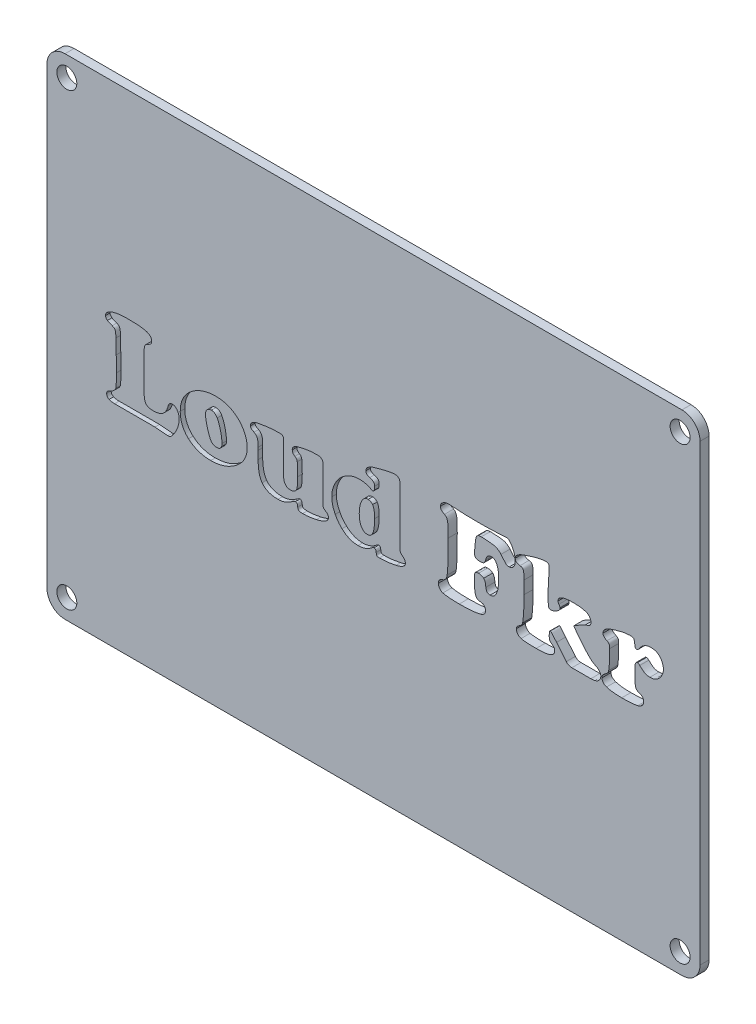
SolidWorks part; units mm, degrees
ref_plane "Front Plane" through (0, 0, 0) normal (0, 0, 1) x (1, 0, 0)
ref_plane "Top Plane" through (0, 0, 0) normal (0, 1, 0) x (1, 0, 0)
ref_plane "Right Plane" through (0, 0, 0) normal (1, 0, 0) x (0, 0, -1)
sketch "Sketch1" plane through (0, 0, 0) normal (0, 0, 1) x (1, 0, 0)
  line L1 (0, 0) -> (91.44, 0)
  line L2 (0, 0) -> (0, -68.58)
  line L3 (0, -68.58) -> (91.44, -68.58)
  line L4 (91.44, 0) -> (91.44, -68.58)
  circle A0 centre (2.794, -2.794) radius 1.397
  circle A1 centre (88.646, -2.794) radius 1.397
  circle A2 centre (88.646, -65.786) radius 1.397
  circle A3 centre (2.794, -65.786) radius 1.397
  dimension "D3" = 2.794
  dimension "D5" = 2.794
  dimension "D6" = 2.794
  dimension "D7" = 2.794
  dimension "D8" = 2.794
  dimension "D9" = 2.794
  dimension "D11" = 2.794
  dimension "D1" = 91.44
  dimension "D2" = 68.58
  dimension "D4" = 2.794
  dimension "D10" = 2.794
extrude "Boss-Extrude1" add sketch "Sketch1" along normal blind 1.27
fillet "Fillet1" radius 2.54 4 edges at (0, 0, 0.635) (91.44, 0, 0.635) (91.44, -68.58, 0.635) (0, -68.58, 0.635)
sketch "Sketch2" plane through (0, 0, 1.27) normal (0, 0, 1) x (1, 0, 0)
  text T0 "Loud Fkr" font "Cooper Black" height in points 48
extrude "Cut-Extrude1" cut sketch "Sketch2" against normal blind 0.635
sketch "Sketch3" plane through (0, 0, 0.635) normal (0, 0, 1) x (1, 0, 0)
  line L0 (66.7892, -31.6857) -> (66.7892, -33.4729) construction
  line L1 (71.3511, -36.9562) -> (72.7156, -38.6162) construction
  line L2 (73.4963, -38.9669) -> (76.1556, -38.9669) construction
  line L3 (70.186, -30.9338) -> (70.3253, -28.3081) construction
  line L4 (66.7892, -31.6857) -> (66.7892, -33.4729)
  line L5 (71.3511, -36.9562) -> (72.7156, -38.6162)
  line L6 (73.4963, -38.9669) -> (76.1556, -38.9669)
  line L7 (70.186, -30.9338) -> (70.3253, -28.3081)
  spline S0 degree 3 poles (-170.7632, 2958.1815) (106.3722, -73.5964) (91.4248, -29.2586) (80.671, -31.0743) (66.0724, -34.3089) (63.1828, -81.1827) (-728.6511, 2857.4668) knots -14.617327 -14.617327 -14.617327 -14.617327 0.212368 0.449686 0.710951 21.260048 21.260048 21.260048 21.260048 only from (81.64, -30.9722) to (79.5548, -31.371) construction
  spline S1 degree 3 poles (-825.1564, 2828.73) (114.102, -59.6144) (90.4479, -27.2547) (78.7878, -31.6269) (78.4908, -31.7605) (78.2561, -31.9003) (78.0767, -32.0488) (77.9531, -32.2145) (76.1625, -36.1636) (123.2831, -50.8524) (-2853.7606, 602.779) knots -16.237622 -16.237622 -16.237622 -16.237622 0.199828 0.371438 0.517594 0.637595 0.738513 0.828644 0.914149 6.474512 6.474512 6.474512 6.474512 only from (79.5548, -31.371) to (77.8588, -32.5865) construction
  spline S2 degree 3 poles (-2908.749, -313.9235) (106.7181, -22.7227) (77.0661, -29.2287) (77.8887, -32.7896) (77.934, -32.8809) (77.9918, -32.9678) (78.0713, -33.0443) (78.1647, -33.116) (82.3292, -35.6086) (100.2272, -10.2745) (-1240.0156, -2727.9166) knots -11.71609 -11.71609 -11.71609 -11.71609 0.115036 0.227451 0.339455 0.4525 0.573047 0.704114 0.843903 16.670206 16.670206 16.670206 16.670206 only from (77.8588, -32.5865) to (78.3993, -33.2375) construction
  spline S3 degree 3 poles (1440.895, 2639.4294) (57.3169, -57.6644) (75.329, -31.1387) (78.5908, -33.3452) (78.6575, -33.4147) (78.7093, -33.493) (78.7421, -33.5895) (78.7656, -33.7073) (79.3419, -39.92) (51.3203, -46.9959) (3077.7419, 42.3684) knots -12.224434 -12.224434 -12.224434 -12.224434 0.12657 0.239338 0.339416 0.434335 0.538529 0.66468 0.819824 20.54905 20.54905 20.54905 20.54905 only from (78.3993, -33.2375) to (78.7813, -34.011) construction
  spline S4 degree 3 poles (3069.4439, 181.1568) (67.881, 49.4355) (79.0587, 7.4997) (78.7762, -34.9104) (78.763, -35.3075) (78.7484, -35.6655) (78.734, -35.9853) (78.7083, -36.2662) (77.9331, -44.1995) (49.9399, -48.3942) (3048.6074, -457.6932) knots -46.327554 -46.327554 -46.327554 -46.327554 0.175004 0.335874 0.481775 0.613575 0.73129 0.835077 0.924873 9.525807 9.525807 9.525807 9.525807 only from (78.7813, -34.011) to (78.6492, -36.7232) construction
  spline S5 degree 3 poles (2975.5785, -815.9956) (36.8367, -16.2457) (80.6157, -32.9052) (78.5467, -37.045) (78.4695, -37.1336) (78.3957, -37.2013) (74.4468, -40.3281) (54.3604, -20.5164) (1795.04, -2497.2498) knots -16.500137 -16.500137 -16.500137 -16.500137 0.247378 0.457288 0.563995 0.687456 0.833114 19.463636 19.463636 19.463636 19.463636 only from (78.6492, -36.7232) to (78.1975, -37.343) construction
  spline S6 degree 3 poles (-1884.825, 2231.129) (118.4705, -65.583) (81.8858, -33.0087) (77.8245, -37.6813) (75.7774, -41.7403) (124.2984, -58.3487) (-2835.71, 676.5601) knots -19.001034 -19.001034 -19.001034 -19.001034 0.295613 0.549866 0.778257 14.63712 14.63712 14.63712 14.63712 only from (78.1975, -37.343) to (77.7051, -38.0901) construction
  spline S7 degree 3 poles (-2898.4574, -414.7237) (113.5229, -25.9965) (76.7442, -34.6126) (77.7427, -38.3473) (77.7929, -38.4628) (77.8664, -38.5657) (77.9575, -38.6605) (78.072, -38.7405) (82.6321, -41.2439) (101.1672, -12.8996) (-1149.5622, -2775.9812) knots -10.194828 -10.194828 -10.194828 -10.194828 0.123517 0.239308 0.352563 0.467914 0.584601 0.712223 0.850057 14.845664 14.845664 14.845664 14.845664 only from (77.7051, -38.0901) to (78.3537, -38.8708) construction
  spline S8 degree 3 poles (-745.1205, -2923.465) (72.538, -7.2879) (71.6582, -37.3594) (78.765, -38.9816) (78.9998, -39.0252) (79.2554, -39.061) (79.5321, -39.0864) (79.8292, -39.1056) (93.9904, -39.635) (108.5253, -14.9275) (65.8704, -3038.8187) knots -9.861662 -9.861662 -9.861662 -9.861662 0.093367 0.195589 0.305873 0.426654 0.555796 0.693584 0.842365 20.33559 20.33559 20.33559 20.33559 only from (78.3537, -38.8708) to (80.4797, -39.1206) construction
  spline S9 degree 3 poles (74.0207, -3038.8532) (47.7313, -17.3966) (64.554, -39.4858) (81.1628, -39.1119) (81.4753, -39.1013) (81.7642, -39.0804) (82.0328, -39.061) (82.2776, -39.0307) (89.9152, -38.0391) (92.7459, -8.8952) (601.0963, -2993.6536) knots -21.815441 -21.815441 -21.815441 -21.815441 0.158822 0.30909 0.447624 0.577752 0.697257 0.808533 0.908239 11.01373 11.01373 11.01373 11.01373 only from (80.4797, -39.1206) to (82.709, -38.9597) construction
  spline S10 degree 3 poles (1000.4644, -2894.9934) (61.3967, -5.4457) (78.3493, -40.9789) (83.0508, -38.8415) (83.1959, -38.7486) (83.3194, -38.6341) (83.4206, -38.5057) (83.494, -38.364) (84.7329, -34.2275) (45.1105, -24.2212) (3054.2142, -456.1516) knots -11.103807 -11.103807 -11.103807 -11.103807 0.139641 0.271259 0.399563 0.52391 0.646565 0.763642 0.879393 10.224905 10.224905 10.224905 10.224905 only from (82.709, -38.9597) to (83.5474, -38.0516) construction
  spline S11 degree 3 poles (3056.506, 363.213) (48.3456, -50.2143) (84.5043, -41.4516) (83.5096, -37.8004) (83.4627, -37.6865) (83.3894, -37.586) (83.2985, -37.4955) (83.1874, -37.4147) (78.5814, -34.9656) (60.9978, -62.968) (1248.7818, 2726.7358) knots -10.205234 -10.205234 -10.205234 -10.205234 0.121723 0.240035 0.352793 0.465684 0.58649 0.711934 0.849722 15.182419 15.182419 15.182419 15.182419 only from (83.5474, -38.0516) to (82.9108, -37.2901) construction
  spline S12 degree 3 poles (-1061.4281, -2810.3508) (103.5543, -10.5116) (86.7131, -39.2214) (82.6799, -37.1953) (82.595, -37.1519) (82.5326, -37.1018) (82.488, -37.0388) (82.4511, -36.9633) (80.9684, -32.4585) (104.625, -21.5695) (-2827.7791, -764.8826) knots -16.589117 -16.589117 -16.589117 -16.589117 0.177067 0.324578 0.44242 0.536942 0.623476 0.731722 0.853236 18.501372 18.501372 18.501372 18.501372 only from (82.9108, -37.2901) to (82.3943, -36.7616) construction
  spline S13 degree 3 poles (-2879.904, -509.1927) (99.8682, -50.2934) (83.3188, -44.5962) (82.3584, -36.4833) (82.3485, -36.3108) (82.3345, -36.1148) (82.3298, -35.8936) (82.3204, -35.6478) (82.3045, -16.9996) (66.0237, 1.188) (3079.4088, 89.8548) knots -14.380209 -14.380209 -14.380209 -14.380209 0.073931 0.163538 0.265758 0.383742 0.515939 0.66249 0.824783 33.957188 33.957188 33.957188 33.957188 only from (82.3943, -36.7616) to (82.3174, -35.0921) construction
  spline S14 degree 3 poles (-2914.9621, -157.4498) (105.6314, -65.9013) (81.841, -50.5128) (82.3298, -34.4389) (82.3519, -34.2058) (82.3754, -34.0336) (82.4224, -33.9115) (82.4869, -33.8244) (84.8387, -32.4761) (97.7145, -73.7364) (-631.5353, 2879.6942) knots -31.542553 -31.542553 -31.542553 -31.542553 0.248352 0.45198 0.60646 0.717088 0.798309 0.865617 0.930201 6.031889 6.031889 6.031889 6.031889 only from (82.3174, -35.0921) to (82.6801, -33.7636) construction
  spline S15 degree 3 poles (725.609, 2896.4646) (70.9659, -65.966) (80.6649, -32.8408) (82.8366, -33.8042) (85.9625, -35.9255) (69.1146, -62.7433) (1976.0199, 2293.3342) knots -18.49071 -18.49071 -18.49071 -18.49071 0.205351 0.432269 0.692833 31.125584 31.125584 31.125584 31.125584 only from (82.6801, -33.7636) to (82.9948, -33.9318) construction
  spline S16 degree 3 poles (-1980.681, -2211.0968) (89.8871, 1.7045) (75.8507, -27.8456) (83.3906, -34.2923) (83.5618, -34.4214) (83.7159, -34.5198) (83.8721, -34.5852) (84.0376, -34.6303) (90.2059, -35.5159) (98.5754, -2.3752) (-96.2113, -3029.0143) knots -17.584319 -17.584319 -17.584319 -17.584319 0.178428 0.333564 0.462741 0.568763 0.665441 0.769786 0.880304 11.980379 11.980379 11.980379 11.980379 only from (82.9948, -33.9318) to (84.4122, -34.6621) construction
  spline S17 degree 3 poles (470.5199, -3009.5759) (63.2425, 14.1835) (77.7411, -36.6045) (85.106, -34.5507) (91.6728, -31.2399) (67.5854, 15.7914) (1819.6265, -2482.1499) knots -15.616756 -15.616756 -15.616756 -15.616756 0.260148 0.507464 0.750107 15.990967 15.990967 15.990967 15.990967 only from (84.4122, -34.6621) to (85.6782, -34.172) construction
  spline S18 degree 3 poles (2305.914, -2051.5902) (51.2649, -17.4825) (82.6226, -38.3314) (85.9357, -33.8788) (86.0457, -33.707) (86.1402, -33.5204) (86.215, -33.325) (86.2756, -33.1309) (87.2457, -26.9551) (55.4103, -18.525) (3079.9347, -226.505) knots -9.984776 -9.984776 -9.984776 -9.984776 0.119758 0.242663 0.368645 0.501357 0.633279 0.759893 0.881364 12.291876 12.291876 12.291876 12.291876 only from (85.6782, -34.172) to (86.3148, -32.7451) construction
  spline S19 degree 3 poles (3077.3728, 198.2119) (55.6285, -46.2164) (87.163, -37.9971) (86.2809, -32.3981) (86.2352, -32.2203) (86.1703, -32.0424) (86.093, -31.8714) (86.0064, -31.7115) (82.6965, -27.074) (55.4968, -42.574) (2372.5013, 1910.2151) knots -11.484968 -11.484968 -11.484968 -11.484968 0.119383 0.241659 0.369919 0.503739 0.638231 0.762971 0.884553 12.547518 12.547518 12.547518 12.547518 only from (86.3148, -32.7451) to (85.7935, -31.4454) construction
  spline S20 degree 3 poles (1855, 2391.2317) (65.8791, -80.976) (91.3722, -34.184) (85.2556, -31.0783) (78.0851, -29.0698) (63.7899, -80.2161) (468.1283, 2944.274) knots -14.507496 -14.507496 -14.507496 -14.507496 0.243928 0.485086 0.734928 16.822338 16.822338 16.822338 16.822338 only from (85.7935, -31.4454) to (84.5803, -30.9722) construction
  spline S21 degree 3 poles (-152.8011, 2959.5352) (101.2306, -68.6005) (90.9677, -29.7514) (84.0799, -31.0283) (83.8482, -31.1096) (83.6263, -31.2177) (83.4189, -31.3616) (83.2245, -31.5364) (78.1902, -37.0151) (107.013, -68.4669) (-2306.5068, 1781.7045) knots -9.770699 -9.770699 -9.770699 -9.770699 0.12477 0.244354 0.362474 0.4806 0.601954 0.728057 0.859866 11.380233 11.380233 11.380233 11.380233 only from (84.5803, -30.9722) to (82.8795, -31.9739) construction
  spline S22 degree 3 poles (2405.5215, -1930.6155) (61.3253, -4.562) (85.4773, -29.4124) (82.7358, -32.1482) (80.7504, -33.3754) (67.1225, 3.7411) (950.4761, -2903.8348) knots -27.900202 -27.900202 -27.900202 -27.900202 0.310732 0.575938 0.794486 17.211322 17.211322 17.211322 17.211322 only from (82.8795, -31.9739) to (82.5696, -32.2069) construction
  spline S23 degree 3 poles (-1144.332, -2769.6414) (106.3197, 10.6892) (83.9751, -33.796) (82.3917, -32.1145) (80.7762, -28.638) (121.9866, -12.2247) (-2791.9323, -890.8948) knots -13.111754 -13.111754 -13.111754 -13.111754 0.207665 0.415515 0.66922 24.321325 24.321325 24.321325 24.321325 only from (82.5696, -32.2069) to (82.3174, -31.8562) construction
  spline S24 degree 3 poles (3067.7442, 262.1114) (51.0766, -52.7805) (83.8999, -40.2483) (82.246, -31.3622) (82.2098, -31.2031) (82.1645, -31.0911) (82.0807, -31.0304) (81.9689, -30.9937) (75.8034, -30.2603) (68.9586, -62.2274) (129.311, 2968.5373) knots -19.866925 -19.866925 -19.866925 -19.866925 0.220788 0.391987 0.515403 0.592337 0.656819 0.7416 0.856841 14.63423 14.63423 14.63423 14.63423 only from (82.3174, -31.8562) to (81.64, -30.9722) construction
  spline S25 degree 3 poles (3056.9434, 253.2298) (36.376, -37.2414) (70.9974, -30.9841) (70.3068, -28.1304) (70.2762, -28.0566) (70.2258, -27.9979) (70.1621, -27.9509) (70.0817, -27.9201) (66.4709, -27.2007) (59.7686, -57.117) (363.0983, 2957.62) knots -12.196518 -12.196518 -12.196518 -12.196518 0.138168 0.262144 0.371886 0.479765 0.590964 0.710234 0.84771 16.405009 16.405009 16.405009 16.405009 only from (70.3253, -28.3081) to (69.8857, -27.8973) construction
  spline S26 degree 3 poles (-128.6029, 2965.3902) (88.2, -61.2636) (77.4899, -26.8637) (69.3017, -27.9453) (68.9644, -28.0016) (68.5951, -28.0888) (68.1905, -28.193) (67.7537, -28.3282) (50.6232, -33.822) (43.8437, -69.3815) (-945.6435, 2795.0121) knots -7.445123 -7.445123 -7.445123 -7.445123 0.084133 0.179355 0.285949 0.404463 0.534789 0.677468 0.83291 17.393172 17.393172 17.393172 17.393172 only from (69.8857, -27.8973) to (66.7892, -28.6564) construction
  spline S27 degree 3 poles (-960.0132, 2789.9954) (97.2707, -50.6993) (76.0586, -24.5375) (66.235, -28.8815) (66.0227, -29.0031) (65.8495, -29.1187) (65.7198, -29.2442) (65.6281, -29.3769) (64.1916, -32.7582) (106.2206, -44.9578) (-2875.6056, 560.0907) knots -18.558625 -18.558625 -18.558625 -18.558625 0.193779 0.362605 0.506685 0.62832 0.732004 0.825188 0.914008 7.155578 7.155578 7.155578 7.155578 only from (66.7892, -28.6564) to (65.5593, -29.6654) construction
  spline S28 degree 3 poles (-2886.5254, -562.9766) (103.0342, -16.9539) (64.5406, -27.0288) (65.5997, -29.8742) (65.6497, -29.9655) (65.7282, -30.0391) (65.8228, -30.1069) (65.9424, -30.1534) (70.5686, -31.6239) (83.4822, 1.6724) (-619.1433, -2950.7921) knots -9.018016 -9.018016 -9.018016 -9.018016 0.115041 0.222983 0.326822 0.436051 0.554232 0.687055 0.832866 15.641317 15.641317 15.641317 15.641317 only from (65.5593, -29.6654) to (66.2319, -30.2203) construction
  spline S29 degree 3 poles (726.5858, 2895.9614) (48.9397, -68.2124) (62.4813, -28.5382) (66.5318, -30.3089) (66.633, -30.4034) (66.6915, -30.5026) (66.7162, -30.6011) (66.7401, -30.694) (66.7511, -30.8097) (66.7677, -30.9446) (66.7744, -31.1011) (66.787, -31.2771) (66.7385, -43.3243) (85.5599, -54.5525) (-2928.9587, -187.9453) knots -7.183649 -7.183649 -7.183649 -7.183649 0.096822 0.181482 0.256196 0.33052 0.374782 0.429664 0.494633 0.573223 0.66252 0.762767 0.875214 21.280715 21.280715 21.280715 21.280715 only from (66.2319, -30.2203) to (66.7892, -31.6857) construction
  spline S30 degree 3 poles (3064.8561, 47.3267) (47.0122, 23.9496) (67.1207, -5.2471) (66.7815, -34.5717) (66.7664, -35.0697) (66.7482, -35.5287) (66.7224, -35.9493) (66.688, -36.3312) (65.5146, -47.5085) (35.139, -54.6332) (3035.148, -468.8011) knots -24.481411 -24.481411 -24.481411 -24.481411 0.162748 0.315294 0.456309 0.586484 0.705885 0.814574 0.912557 10.260175 10.260175 10.260175 10.260175 only from (66.7892, -33.4729) to (66.6018, -36.9922) construction
  spline S31 degree 3 poles (2912.1412, -986.653) (26.5702, -14.3071) (68.8051, -33.3282) (66.4826, -37.2896) (66.4006, -37.3649) (66.3156, -37.429) (59.3598, -42.1075) (41.465, -29.4008) (1647.0889, -2587.0163) knots -15.768122 -15.768122 -15.768122 -15.768122 0.234604 0.41553 0.507764 0.635862 0.800634 30.832635 30.832635 30.832635 30.832635 only from (66.6018, -36.9922) to (66.0709, -37.588) construction
  spline S32 degree 3 poles (-1838.0458, 2280.4736) (99.8845, -63.2712) (69.2232, -34.0924) (65.7983, -37.827) (64.1627, -41.1112) (107.9362, -55.02) (-2856.83, 638.9011) knots -21.566339 -21.566339 -21.566339 -21.566339 0.292044 0.544315 0.776889 16.235573 16.235573 16.235573 16.235573 only from (66.0709, -37.588) to (65.713, -38.1261) construction
  spline S33 degree 3 poles (-2910.5285, -414.2994) (100.8297, -25.8584) (64.6799, -34.5298) (65.7577, -38.3991) (65.8226, -38.5287) (65.9041, -38.6551) (66.0074, -38.7658) (66.1205, -38.8618) (69.822, -41.0139) (87.5096, -9.9071) (-1088.9253, -2807.5716) knots -9.962967 -9.962967 -9.962967 -9.962967 0.11887 0.237303 0.361812 0.49376 0.626099 0.752977 0.877694 11.651298 11.651298 11.651298 11.651298 only from (65.713, -38.1261) to (66.3808, -38.9813) construction
  spline S34 degree 3 poles (-532.7881, -2978.3985) (62.7222, -7.6694) (61.6852, -38.4201) (66.7089, -39.0428) (66.9209, -39.0685) (67.1687, -39.0856) (67.4512, -39.1041) (67.7701, -39.1113) (84.6173, -39.5146) (101.7454, -15.6155) (70.2744, -3038.7555) knots -6.865346 -6.865346 -6.865346 -6.865346 0.067293 0.15167 0.251557 0.368074 0.501392 0.650334 0.817288 24.237235 24.237235 24.237235 24.237235 only from (66.3808, -38.9813) to (68.502, -39.1206) construction
  spline S35 degree 3 poles (23.0278, -3038.3983) (33.7544, -20.3653) (51.4206, -39.5627) (69.1381, -39.1088) (69.424, -39.0889) (69.6854, -39.0635) (69.9218, -39.0297) (70.1341, -38.9906) (70.3212, -38.939) (70.487, -38.8854) (70.6305, -38.82) (70.7543, -38.7456) (70.8595, -38.6614) (70.9435, -38.566) (71.0146, -38.4646) (71.0579, -38.3496) (72.0249, -34.5932) (36.209, -25.8228) (3044.5075, -435.4273) knots -17.009074 -17.009074 -17.009074 -17.009074 0.108755 0.209724 0.303032 0.388739 0.466185 0.536303 0.599498 0.655657 0.706418 0.753109 0.796485 0.83748 0.876971 0.916631 0.956858 4.649146 4.649146 4.649146 4.649146 only from (68.502, -39.1206) to (71.0941, -38.0973) construction
  spline S36 degree 3 poles (3036.5641, 415.0445) (31.4141, -51.7261) (72.3081, -41.4923) (71.0404, -37.815) (68.9758, -34.8106) (36.9451, -62.1889) (2172.3602, 2103.1619) knots -19.662201 -19.662201 -19.662201 -19.662201 0.265455 0.513436 0.752239 19.363535 19.363535 19.363535 19.363535 only from (71.0941, -38.0973) to (70.8514, -37.6144) construction
  spline S37 degree 3 poles (-1664.8231, -2484.3703) (98.2936, -22.12) (75.9069, -41.6619) (70.5805, -37.4151) (70.4852, -37.3251) (70.4154, -37.2356) (70.3731, -37.1336) (70.3463, -37.0142) (69.6201, -31.9175) (103.433, -24.633) (-2924.2454, -214.9014) knots -17.913725 -17.913725 -17.913725 -17.913725 0.168873 0.310118 0.427652 0.521763 0.613594 0.722485 0.851002 14.458479 14.458479 14.458479 14.458479 only from (70.8514, -37.6144) to (70.3253, -36.7136) construction
  spline S38 degree 3 poles (-2928.5199, -112.9159) (85.9935, -59.9714) (70.0507, -48.3081) (70.3308, -36.3835) (70.34, -36.2624) (70.3528, -36.1701) (70.3741, -36.1021) (70.4023, -36.0534) (71.5679, -35.1458) (84.6486, -67.8822) (-928.3842, 2792.134) knots -46.130734 -46.130734 -46.130734 -46.130734 0.244817 0.445775 0.603197 0.720836 0.810157 0.880685 0.939063 6.354231 6.354231 6.354231 6.354231 only from (70.3253, -36.7136) to (70.4887, -36.0169) construction
  spline S39 degree 3 poles (1490.5621, 2606.3627) (46.455, -70.7483) (68.9455, -34.2049) (70.6702, -36.1235) (70.7313, -36.193) (70.7826, -36.2502) (70.8429, -36.3279) (70.9219, -36.4184) (71.0094, -36.5292) (71.1105, -36.657) (83.0873, -51.6163) (103.5972, -59.5723) (-2220.2995, -1972.3551) knots -5.498883 -5.498883 -5.498883 -5.498883 0.074818 0.189608 0.231843 0.291251 0.36806 0.460606 0.570579 0.696555 0.839694 45.151044 45.151044 45.151044 45.151044 only from (70.4887, -36.0169) to (71.3511, -36.9562) construction
  spline S40 degree 3 poles (-1872.7656, -2322.093) (96.4175, 3.7192) (68.7889, -36.4169) (73.0494, -38.8838) (78.2298, -40.5854) (91.4176, 6.0126) (-406.0741, -3000.2425) knots -15.759319 -15.759319 -15.759319 -15.759319 0.243925 0.481491 0.729733 18.56586 18.56586 18.56586 18.56586 only from (72.7156, -38.6162) to (73.4963, -38.9669) construction
  spline S41 degree 3 poles (343.7463, -3026.96) (57.9658, 4.3286) (69.5326, -40.3407) (76.7282, -38.9048) (76.971, -38.8228) (77.1777, -38.7026) (77.3437, -38.5501) (77.467, -38.3695) (79.1687, -33.3266) (32.9756, -21.1543) (3046.2193, -469.011) knots -10.796707 -10.796707 -10.796707 -10.796707 0.157699 0.299319 0.428494 0.549809 0.663845 0.772003 0.882487 8.721683 8.721683 8.721683 8.721683 only from (76.1556, -38.9669) to (77.5513, -37.9339) construction
  spline S42 degree 3 poles (3043.193, 413.9639) (43.7618, -49.7931) (78.4729, -40.994) (77.514, -37.7105) (77.4701, -37.6011) (77.4005, -37.4984) (77.3152, -37.3983) (77.2106, -37.3024) (72.5477, -33.7371) (50.7551, -55.6195) (1741.7169, 2458.488) knots -9.307008 -9.307008 -9.307008 -9.307008 0.106981 0.212607 0.323391 0.439768 0.562029 0.695225 0.840836 17.16262 17.16262 17.16262 17.16262 only from (77.5513, -37.9339) to (76.9484, -37.122) construction
  spline S43 degree 3 poles (-1277.132, -2713.9615) (103.1773, -18.6334) (83.2877, -40.6641) (76.6031, -36.9451) (76.4574, -36.8629) (76.3283, -36.7742) (76.2003, -36.6701) (76.0567, -36.5437) (62.6397, -23.2734) (59.9989, -0.3675) (-2188.5094, -2003.6857) knots -14.452321 -14.452321 -14.452321 -14.452321 0.13459 0.254677 0.362428 0.458378 0.557704 0.681889 0.828887 37.103902 37.103902 37.103902 37.103902 only from (76.9484, -37.122) to (75.716, -36.2043) construction
  spline S44 degree 3 poles (-2134.2156, -2064.5386) (118.649, -47.716) (87.5451, -49.9653) (75.0942, -35.4971) (74.769, -35.1047) (74.4983, -34.7634) (74.2854, -34.4963) (74.1488, -34.3146) (74.0312, -34.1597) (73.9357, -34.0298) (73.859, -33.9269) (73.8082, -33.8462) (72.9279, -32.6511) (92.7182, -22.0075) (-2653.6721, -1280.4572) knots -17.772841 -17.772841 -17.772841 -17.772841 0.143557 0.29704 0.458926 0.630345 0.713129 0.785183 0.847446 0.898847 0.939393 0.96973 0.990325 2.335791 2.335791 2.335791 2.335791 only from (75.716, -36.2043) to (73.7582, -33.754) construction
  spline S45 degree 3 poles (-1692.0228, 2391.4197) (82.3106, -59.2256) (70.4161, -35.7561) (73.9987, -33.5882) (74.2014, -33.468) (74.453, -33.3307) (74.7178, -33.1861) (74.967, -33.0486) (87.0859, -26.1932) (106.9095, -33.3642) (-1348.328, 2607.582) knots -6.409158 -6.409158 -6.409158 -6.409158 0.053789 0.14364 0.2699 0.430941 0.601686 0.752405 0.885965 22.863824 22.863824 22.863824 22.863824 only from (73.7582, -33.754) to (75.3821, -32.8171) construction
  spline S46 degree 3 poles (816.73, -2939.6151) (55.0847, -12.6884) (68.4985, -34.6539) (75.672, -32.7479) (78.4328, -32.0689) (73.9323, -10.0839) (1045.565, -2871.391) knots -46.75133 -46.75133 -46.75133 -46.75133 0.373704 0.665117 0.873183 18.557643 18.557643 18.557643 18.557643 only from (75.3821, -32.8171) to (75.8337, -32.697) construction
  spline S47 degree 3 poles (1963.7584, -2364.022) (39.388, 0.3353) (73.6567, -35.6196) (76.092, -32.4707) (77.7027, -28.3072) (31.5595, -15.3961) (3028.6216, -563.568) knots -15.764449 -15.764449 -15.764449 -15.764449 0.249231 0.483307 0.72701 18.871181 18.871181 18.871181 18.871181 only from (75.8337, -32.697) to (76.1676, -32.1157) construction
  spline S48 degree 3 poles (3056.4898, 309.6043) (43.3167, -44.5115) (77.128, -36.1275) (76.1276, -31.8365) (76.0722, -31.7043) (75.9941, -31.5809) (75.9045, -31.4651) (75.7992, -31.3669) (72.2124, -28.954) (52.3328, -57.9777) (1448.4615, 2635.9907) knots -11.147975 -11.147975 -11.147975 -11.147975 0.124649 0.245673 0.371172 0.499707 0.628587 0.755194 0.876637 11.929714 11.929714 11.929714 11.929714 only from (76.1676, -32.1157) to (75.5526, -31.2316) construction
  spline S49 degree 3 poles (885.8896, 2857.049) (81.1202, -78.1314) (83.9509, -32.6928) (74.7514, -31.0282) (61.0996, -29.6949) (45.3118, -71.5708) (192.1267, 2966.3891) knots -14.52152 -14.52152 -14.52152 -14.52152 0.206856 0.440039 0.704247 22.595795 22.595795 22.595795 22.595795 only from (75.5526, -31.2316) to (73.7437, -30.9722) construction
  spline S50 degree 3 poles (21.0192, 2968.4438) (93.0248, -59.6629) (82.7687, -30.4508) (73.2343, -30.986) (73.0026, -31.0011) (72.7871, -31.0256) (72.5888, -31.0556) (72.4088, -31.0947) (72.2449, -31.1365) (72.0998, -31.1906) (71.968, -31.2455) (71.8575, -31.3154) (71.7597, -31.3854) (71.6815, -31.4663) (71.6203, -31.5538) (71.5762, -31.6479) (70.7343, -35.1892) (101.8597, -42.3248) (-2910.2623, 296.0426) knots -10.761553 -10.761553 -10.761553 -10.761553 0.102884 0.198461 0.288598 0.371606 0.449472 0.520549 0.584849 0.644951 0.699721 0.749633 0.795975 0.838579 0.879202 0.919013 0.958128 5.063128 5.063128 5.063128 5.063128 only from (73.7437, -30.9722) to (71.5457, -31.8562) construction
  spline S51 degree 3 poles (-2735.3578, -1090.5092) (114.3444, -8.2819) (23.6497, -50.5146) (125.1556, -19.5048) (-2727.607, -1110.5697) knots -29.199025 -29.199025 -29.199025 -29.199025 0.455588 31.985831 31.985831 31.985831 31.985831 only from (71.5457, -31.8562) to (71.6754, -32.1829) construction
  spline S52 degree 3 poles (-2720.5849, -1128.7752) (72.3708, -10.5623) (65.8618, -23.971) (71.8086, -32.3733) (72.7441, -34.5235) (49.3312, -43.1206) (2972.4828, 732.9212) knots -81.228932 -81.228932 -81.228932 -81.228932 0.358481 0.640618 0.855669 18.894144 18.894144 18.894144 18.894144 only from (71.6754, -32.1829) to (71.8532, -32.5096) construction
  spline S53 degree 3 poles (2928.6818, -948.0821) (24.3909, -9.8433) (73.8632, -29.6842) (71.7214, -32.8626) (71.5562, -33.0205) (71.3381, -33.1545) (71.1103, -33.2697) (70.9019, -33.3603) (66.8266, -34.7112) (55.9625, 1.5581) (597.1514, -2986.769) knots -6.243665 -6.243665 -6.243665 -6.243665 0.105271 0.218004 0.350535 0.509628 0.668999 0.803223 0.912828 8.223548 8.223548 8.223548 8.223548 only from (71.8532, -32.5096) to (70.5632, -33.4321) construction
  spline S54 degree 3 poles (-731.324, -2924.1577) (89.3149, 12.3033) (72.964, -35.0242) (70.313, -33.35) (68.2322, -30.4456) (112.6364, -8.993) (-2718.8712, -1137.8672) knots -15.745939 -15.745939 -15.745939 -15.745939 0.251401 0.476303 0.713326 19.199684 19.199684 19.199684 19.199684 only from (70.5632, -33.4321) to (70.198, -33.0886) construction
  spline S55 degree 3 poles (-2911.1248, -364.2693) (90.5922, -35.8164) (70.2778, -35.5025) (70.1861, -32.962) (70.1799, -32.8693) (70.179, -32.7554) (70.176, -32.6193) (70.174, -32.4624) (69.9829, -21.7122) (89.3386, -10.8709) (-2929.6325, -22.4704) knots -7.398883 -7.398883 -7.398883 -7.398883 0.048571 0.120781 0.212171 0.327476 0.461991 0.62052 0.79826 32.708925 32.708925 32.708925 32.708925 only from (70.198, -33.0886) to (70.1716, -32.0892) construction
  spline S56 degree 3 poles (-2929.5938, -45.1935) (96.3165, -59.7541) (69.823, -45.5124) (70.1776, -31.4351) (70.1509, -21.6617) (94.1825, -12.471) (-2928.3552, 57.2299) knots -35.743946 -35.743946 -35.743946 -35.743946 0.309727 0.579991 0.808658 25.676384 25.676384 25.676384 25.676384 only from (70.1716, -32.0892) to (70.186, -30.9338) construction
  spline S57 degree 3 poles (61.2855, 2970.1575) (20.0872, -44.3877) (40.887, -28.5712) (61.438, -29.4591) (61.7141, -29.4801) (61.9643, -29.4971) (62.1868, -29.522) (62.3827, -29.5467) (62.5497, -29.579) (62.7369, -29.6183) (62.9449, -29.6928) (63.1751, -29.8161) (68.6364, -34.1655) (43.2432, -69.2017) (2200.3472, 2075.0777) knots -20.589266 -20.589266 -20.589266 -20.589266 0.112354 0.214987 0.30878 0.393647 0.46975 0.536259 0.594187 0.642548 0.730555 0.817567 0.90677 7.78072 7.78072 7.78072 7.78072 only from (60.8124, -29.4347) to (63.5654, -30.1843) construction
  spline S58 degree 3 poles (-2258.7618, -1929.0344) (63.8409, -0.3423) (56.2848, -21.6988) (63.8266, -30.4955) (63.9402, -30.6254) (64.0379, -30.7383) (64.1219, -30.832) (64.1921, -30.9076) (64.2488, -30.9646) (64.3064, -31.0181) (64.381, -31.0619) (64.4791, -31.1024) (68.8513, -31.8402) (74.6208, -1.1045) (-58.7581, -3028.3929) knots -22.04559 -22.04559 -22.04559 -22.04559 0.140881 0.267287 0.378231 0.474888 0.556097 0.621883 0.674483 0.711806 0.773737 0.840502 0.916185 9.292186 9.292186 9.292186 9.292186 only from (63.5654, -30.1843) to (64.7209, -31.1259) construction
  spline S59 degree 3 poles (541.7899, -2992.8425) (49.4052, 10.1213) (60.8533, -32.5226) (65.0622, -31.0577) (65.2087, -30.9631) (65.3334, -30.8317) (65.4334, -30.6691) (65.5091, -30.4819) (66.7335, -24.3877) (26.5082, -14.8299) (3056.0787, -266.7989) knots -8.252299 -8.252299 -8.252299 -8.252299 0.116386 0.227152 0.336888 0.454111 0.57776 0.707553 0.846474 12.641621 12.641621 12.641621 12.641621 only from (64.7209, -31.1259) to (65.5593, -30.0401) construction
  spline S60 degree 3 poles (3062.5334, 101.3752) (33.5336, -48.1819) (66.5011, -38.0041) (65.5208, -29.5094) (65.4634, -29.2538) (65.3901, -29.0023) (65.291, -28.7573) (65.1691, -28.5193) (61.1951, -21.722) (25.3514, -36.6013) (2536.3808, 1672.1282) knots -11.620498 -11.620498 -11.620498 -11.620498 0.126145 0.249659 0.371703 0.493809 0.617502 0.742295 0.86946 11.662636 11.662636 11.662636 11.662636 only from (65.5593, -30.0401) to (64.865, -28.0631) construction
  spline S61 degree 3 poles (2193.989, 2085.249) (43.6484, -62.9628) (68.5686, -30.958) (64.6162, -27.821) (61.4518, -26.3055) (48.1471, -68.1188) (741.9372, 2894.6109) knots -22.791327 -22.791327 -22.791327 -22.791327 0.29552 0.552834 0.783504 16.46288 16.46288 16.46288 16.46288 only from (64.865, -28.0631) to (64.3365, -27.7436) construction
  spline S62 degree 3 poles (-118.4508, 2966.5822) (73.3262, -50.5967) (62.1471, -1.8644) (57.7041, -57.0507) (-142.4135, 2965.0704) knots -55.116386 -55.116386 -55.116386 -55.116386 0.422359 62.180715 62.180715 62.180715 62.180715 only from (64.3365, -27.7436) to (64.1323, -27.758) construction
  spline S63 degree 3 poles (396.6955, -3008.8663) (80.5412, 3.3061) (73.5984, -27.1349) (63.4983, -27.8195) (63.1044, -27.8449) (62.6518, -27.8622) (62.141, -27.8807) (61.5715, -27.8878) (31.9082, -28.2925) (2.2187, -4.3281) (-0.2614, -3026.4396) knots -7.602006 -7.602006 -7.602006 -7.602006 0.072712 0.160104 0.262352 0.379452 0.512076 0.659585 0.822018 23.567338 23.567338 23.567338 23.567338 only from (64.1323, -27.758) to (60.2767, -27.8973) construction
  spline S64 degree 3 poles (113.5807, -3026.6161) (119.8654, 0.7521) (89.1928, -28.5876) (58.6349, -27.8742) (35.4016, -26.8509) (14.3502, 5.4184) (-193.6211, -3016.7036) knots -29.015071 -29.015071 -29.015071 -29.015071 0.280244 0.540259 0.780151 22.947846 22.947846 22.947846 22.947846 only from (60.2767, -27.8973) to (57.2018, -27.7916) construction
  spline S65 degree 3 poles (288.8086, 2963.0529) (80.7232, -52.5316) (69.4946, -28.4544) (56.6798, -27.7561) (48.5984, -27.3253) (39.954, -49.8911) (116.8442, 2971.4402) knots -40.861185 -40.861185 -40.861185 -40.861185 0.310287 0.578544 0.81018 26.582049 26.582049 26.582049 26.582049 only from (57.2018, -27.7916) to (56.2793, -27.7436) construction
  spline S66 degree 3 poles (-237.3435, 2957.748) (72.1429, -67.9211) (61.7942, -26.5143) (55.8249, -27.7979) (55.622, -27.8716) (55.4438, -27.9768) (55.2938, -28.1015) (55.183, -28.2469) (53.6066, -32.1741) (96.88, -44.5869) (-2894.0162, 521.1718) knots -10.981922 -10.981922 -10.981922 -10.981922 0.149063 0.288778 0.421938 0.552623 0.67521 0.785826 0.892438 8.484761 8.484761 8.484761 8.484761 only from (56.2793, -27.7436) to (55.1046, -28.5819) construction
  spline S67 degree 3 poles (-2939.8785, -200.3035) (83.3324, -18.6239) (54.4278, -24.6071) (55.1268, -28.8022) (55.1611, -28.8931) (55.2092, -28.9736) (55.2826, -29.0464) (55.3831, -29.1191) (60.7225, -32.5662) (81.0449, -10.2197) (-1438.6, -2630.4826) knots -12.914671 -12.914671 -12.914671 -12.914671 0.123125 0.235288 0.334507 0.425698 0.526801 0.655716 0.813643 20.417008 20.417008 20.417008 20.417008 only from (55.1046, -28.5819) to (55.6596, -29.281) construction
  spline S68 degree 3 poles (1907.4734, 2330.3822) (20.5174, -60.3372) (53.06, -26.1474) (55.9487, -29.5269) (56.0416, -29.708) (56.0886, -29.8859) (56.1171, -30.0563) (56.131, -30.2211) (56.1499, -30.4194) (56.1599, -30.651) (56.1698, -30.9169) (56.1774, -31.2164) (56.236, -57.0612) (70.957, -82.6295) (-2941.0319, -144.4849) knots -4.497134 -4.497134 -4.497134 -4.497134 0.067575 0.135281 0.206133 0.284891 0.332021 0.391729 0.462581 0.5462 0.640963 0.748608 0.868278 28.426632 28.426632 28.426632 28.426632 only from (55.6596, -29.281) to (56.1809, -31.9067) construction
  spline S69 degree 3 poles (3055.0741, 27.4025) (37.3082, 14.2665) (56.3727, -9.2084) (56.1781, -32.7507) (56.1769, -33.1462) (56.1712, -33.5218) (56.1665, -33.8765) (56.1623, -34.2113) (56.1552, -34.526) (56.1451, -34.8214) (56.1355, -35.0969) (56.1265, -35.3524) (56.1148, -35.587) (56.0998, -35.8016) (56.0853, -35.9961) (56.0718, -36.1717) (55.0706, -45.3059) (38.8625, -52.4492) (3028.3355, -441.3794) knots -15.193875 -15.193875 -15.193875 -15.193875 0.095218 0.186229 0.273032 0.355105 0.43297 0.506101 0.575033 0.639774 0.700308 0.756111 0.807732 0.854658 0.897387 0.935919 0.970311 6.93334 6.93334 6.93334 6.93334 only from (56.1809, -31.9067) to (56.0367, -36.4686) construction
  spline S70 degree 3 poles (2995.0429, -637.7388) (28.7308, -19.8529) (57.436, -31.4544) (55.9724, -36.7623) (55.9235, -36.8898) (55.8598, -37.0012) (55.7876, -37.0994) (55.7023, -37.1819) (52.6151, -39.3755) (33.0535, -11.298) (1482.906, -2675.8613) knots -15.401669 -15.401669 -15.401669 -15.401669 0.152362 0.29105 0.42246 0.544259 0.659513 0.77199 0.884539 11.496159 11.496159 11.496159 11.496159 only from (56.0367, -36.4686) to (55.4962, -37.2997) construction
  spline S71 degree 3 poles (-1162.6122, 2704.1462) (79.4844, -53.0814) (62.3403, -34.1711) (55.211, -37.4218) (52.4803, -38.6119) (60.2493, -59.3667) (-1365.4231, 2604.6634) knots -47.482721 -47.482721 -47.482721 -47.482721 0.374236 0.666106 0.873786 18.706978 18.706978 18.706978 18.706978 only from (55.4962, -37.2997) to (55.0542, -37.5015) construction
  spline S72 degree 3 poles (-2253.6323, 1878.065) (92.7633, -58.325) (56.949, -34.1285) (54.856, -37.7554) (53.5205, -41.9787) (94.4388, -52.7703) (-2910.8398, 413.8114) knots -18.266062 -18.266062 -18.266062 -18.266062 0.25227 0.491224 0.737723 20.389663 20.389663 20.389663 20.389663 only from (55.0542, -37.5015) to (54.7972, -38.0805) construction
  spline S73 degree 3 poles (-2920.7828, -419.2988) (89.3901, -25.5703) (53.7881, -34.3605) (54.8397, -38.354) (54.896, -38.4825) (54.9714, -38.6044) (55.0682, -38.7113) (55.1768, -38.8046) (58.9032, -41.0079) (77.0632, -9.7756) (-1125.622, -2796.4874) knots -10.497993 -10.497993 -10.497993 -10.497993 0.123496 0.243891 0.366454 0.494177 0.621901 0.746845 0.872365 12.007543 12.007543 12.007543 12.007543 only from (54.7972, -38.0805) to (55.4362, -38.9261) construction
  spline S74 degree 3 poles (-641.4382, -2956.6524) (50.5143, -6.8881) (49.6413, -37.9536) (55.8255, -39.0128) (56.0642, -39.0466) (56.335, -39.0752) (56.6378, -39.0964) (56.9727, -39.1097) (72.8843, -39.5645) (89.0604, -13.3609) (62.0855, -3038.8355) knots -7.869823 -7.869823 -7.869823 -7.869823 0.077481 0.168501 0.272536 0.390775 0.522213 0.666979 0.826232 21.204965 21.204965 21.204965 21.204965 only from (55.4362, -38.9261) to (57.7303, -39.1206) construction
  spline S75 degree 3 poles (42.6807, -3038.7133) (19.9709, -14.8324) (39.4007, -39.6366) (58.6177, -39.1055) (59.0269, -39.0862) (59.4092, -39.0614) (59.7648, -39.0246) (60.0932, -38.9816) (69.6957, -37.4511) (73.0811, -5.2258) (673.4462, -2975.4117) knots -18.997791 -18.997791 -18.997791 -18.997791 0.155473 0.302086 0.439889 0.569749 0.689394 0.801278 0.904708 10.516154 10.516154 10.516154 10.516154 only from (57.7303, -39.1206) to (60.6803, -38.8684) construction
  spline S76 degree 3 poles (1008.7705, -2884.9726) (39.7224, -10.6325) (55.852, -40.9653) (60.9971, -38.7563) (61.1257, -38.6774) (61.2264, -38.5792) (61.3097, -38.4713) (61.3674, -38.3468) (62.406, -34.0667) (26.7364, -25.5516) (3042.5185, -372.9005) knots -13.709632 -13.709632 -13.709632 -13.709632 0.150527 0.287472 0.412193 0.529649 0.64103 0.755174 0.874036 11.703904 11.703904 11.703904 11.703904 only from (60.6803, -38.8684) to (61.4082, -38.0612) construction
  spline S77 degree 3 poles (3044.7487, 276.8014) (30.0255, -48.8875) (62.2538, -41.5698) (61.3755, -37.831) (61.3269, -37.7257) (61.2616, -37.6303) (61.1863, -37.5457) (61.0987, -37.4804) (58.2496, -36.0402) (44.1004, -69.3419) (982.9012, 2817.2938) knots -12.371706 -12.371706 -12.371706 -12.371706 0.131719 0.258438 0.387931 0.517229 0.644288 0.764853 0.881083 11.22393 11.22393 11.22393 11.22393 only from (61.4082, -38.0612) to (60.8989, -37.4102) construction
  spline S78 degree 3 poles (2999.5342, 565.4412) (107.6324, -47.4328) (87.6345, -41.6395) (60.5587, -37.3563) (60.4447, -37.3317) (60.3432, -37.3095) (57.1947, -35.303) (83.4612, -4.1825) (-2077.8298, -2140.8947) knots -101.240856 -101.240856 -101.240856 -101.240856 0.247178 0.443447 0.58942 0.681857 0.827374 14.1283 14.1283 14.1283 14.1283 only from (60.8989, -37.4102) to (60.159, -37.1508) construction
  spline S79 degree 3 poles (-2486.0193, -1623.1725) (94.7741, -23.3263) (61.3322, -40.092) (60.0241, -36.9188) (59.9695, -36.755) (59.9329, -36.555) (59.8972, -36.323) (59.8789, -36.0564) (59.2575, -24.2158) (88.8171, -11.4554) (-2939.2768, -101.0229) knots -5.510088 -5.510088 -5.510088 -5.510088 0.065869 0.146518 0.243383 0.358209 0.489695 0.640628 0.810237 20.558067 20.558067 20.558067 20.558067 only from (60.159, -37.1508) to (59.8611, -35.4308) construction
  spline S80 degree 3 poles (-2939.9848, -33.2463) (75.5248, -56.0846) (59.5813, -45.5388) (59.8669, -35.1305) (59.8646, -35.0064) (59.8695, -34.9023) (59.867, -34.8174) (59.8713, -34.7526) (59.821, -31.3578) (67.7745, -28.1308) (-2939.232, 30.1395) knots -40.699819 -40.699819 -40.699819 -40.699819 0.215865 0.40634 0.568222 0.70792 0.819015 0.904776 0.965084 14.272155 14.272155 14.272155 14.272155 only from (59.8611, -35.4308) to (59.8707, -34.6741) construction
  spline S81 degree 3 poles (-2939.9037, -54.8416) (92.7201, -44.8789) (59.3348, -39.6722) (59.8817, -34.3736) (59.9166, -34.2614) (59.9693, -34.1724) (60.0503, -34.1133) (60.1532, -34.0722) (64.8074, -33.2649) (71.4187, -67.5559) (-95.9471, 2961.7326) knots -15.422641 -15.422641 -15.422641 -15.422641 0.167659 0.307584 0.42347 0.517155 0.611055 0.717362 0.846544 14.647424 14.647424 14.647424 14.647424 only from (59.8707, -34.6741) to (60.428, -34.0471) construction
  spline S82 degree 3 poles (429.3697, 2943.0409) (44.4903, -74.9041) (55.446, -32.7581) (60.8377, -34.1045) (64.7665, -35.9029) (42.2367, -75.496) (1788.0674, 2418.7145) knots -20.52069 -20.52069 -20.52069 -20.52069 0.284604 0.538967 0.772115 16.712784 16.712784 16.712784 16.712784 only from (60.428, -34.0471) to (61.1415, -34.3041) construction
  spline S83 degree 3 poles (2491.7289, 1723.9855) (17.175, -54.8395) (59.3697, -30.2947) (61.3492, -34.611) (61.3819, -34.7504) (61.4092, -34.8839) (62.6523, -43.8847) (41.1688, -55.1759) (3048.1349, 244.8073) knots -13.433498 -13.433498 -13.433498 -13.433498 0.209011 0.396121 0.502193 0.636236 0.802857 27.604123 27.604123 27.604123 27.604123 only from (61.1415, -34.3041) to (61.4514, -35.2362) construction
  spline S84 degree 3 poles (-2886.947, -588.6533) (91.2454, -19.5547) (60.1298, -30.6483) (61.5116, -35.5191) (61.5643, -35.6342) (61.6317, -35.729) (61.7127, -35.8045) (61.8099, -35.8552) (65.1426, -36.8447) (73.7308, -0.307) (-346.9134, -3007.7467) knots -15.015932 -15.015932 -15.015932 -15.015932 0.159157 0.299544 0.42673 0.544398 0.653703 0.762264 0.877064 11.196329 11.196329 11.196329 11.196329 only from (61.4514, -35.2362) to (62.0376, -35.892) construction
  spline S85 degree 3 poles (588.4077, -2989.2443) (43.8498, 10.2174) (57.6763, -37.6293) (62.4741, -35.7973) (66.7107, -32.7393) (34.7472, 5.2505) (2228.7378, -2111.033) knots -16.163826 -16.163826 -16.163826 -16.163826 0.255807 0.498746 0.740045 17.472906 17.472906 17.472906 17.472906 only from (62.0376, -35.892) to (62.7967, -35.4836) construction
  spline S86 degree 3 poles (2695.8043, -1473.0326) (24.1467, -27.4774) (60.6846, -40.5481) (63.0001, -35.0951) (63.0811, -34.8679) (63.145, -34.6162) (63.1915, -34.3404) (63.2278, -34.0423) (63.9923, -22.5555) (32.5734, -10.2133) (3062.5374, -88.8734) knots -7.816759 -7.816759 -7.816759 -7.816759 0.09637 0.198957 0.308725 0.42818 0.555706 0.693327 0.841304 16.386118 16.386118 16.386118 16.386118 only from (62.7967, -35.4836) to (63.2531, -33.3817) construction
  spline S87 degree 3 poles (3062.6195, 19.6425) (38.3045, -55.7515) (63.7787, -43.9734) (63.2377, -32.8585) (63.2198, -32.6203) (63.1905, -32.4) (63.1556, -32.1968) (63.1095, -32.0117) (63.0575, -31.8436) (62.9976, -31.6928) (62.9282, -31.5595) (62.8491, -31.4449) (62.7642, -31.3457) (62.6693, -31.2655) (62.5664, -31.2029) (62.4551, -31.1586) (58.5181, -30.2643) (50.7893, -63.374) (386.4496, 2951.2171) knots -11.868233 -11.868233 -11.868233 -11.868233 0.099678 0.192451 0.279282 0.360393 0.434991 0.504326 0.568474 0.626918 0.681275 0.732199 0.778666 0.823329 0.867259 0.90963 0.953534 5.250835 5.250835 5.250835 5.250835 only from (63.2531, -33.3817) to (62.2105, -31.1259) construction
  spline S88 degree 3 poles (-409.7792, 2931.3749) (75.8675, -70.2294) (65.5451, -29.981) (61.9334, -31.1752) (61.8091, -31.2393) (61.7038, -31.338) (61.6052, -31.4553) (61.5276, -31.6048) (59.2713, -37.1065) (92.3966, -54.1599) (-2794.3018, 886.9095) knots -8.58394 -8.58394 -8.58394 -8.58394 0.114049 0.223097 0.330737 0.442112 0.561931 0.691642 0.838676 14.605306 14.605306 14.605306 14.605306 only from (62.2105, -31.1259) to (61.4082, -31.9691) construction
  spline S89 degree 3 poles (2924.5351, -927.5991) (30.0735, -13.5399) (63.0034, -28.3487) (61.3278, -32.2173) (61.27, -32.3147) (61.1947, -32.3903) (61.1024, -32.446) (60.9908, -32.4822) (56.5344, -33.325) (48.8298, 1.7524) (321.0133, -3021.0537) knots -12.453167 -12.453167 -12.453167 -12.453167 0.144286 0.269326 0.384797 0.488657 0.591938 0.711163 0.845602 14.406991 14.406991 14.406991 14.406991 only from (61.4082, -31.9691) to (60.7139, -32.5096) construction
  spline S90 degree 3 poles (-80.2494, -3029.0665) (75.4662, 1.7431) (66.955, -33.3136) (60.3149, -32.4837) (60.1647, -32.4479) (60.0481, -32.3928) (59.9651, -32.3089) (59.9103, -32.2016) (58.8411, -28.0396) (97.2515, -19.2549) (-2920.6589, -371.4161) knots -16.228412 -16.228412 -16.228412 -16.228412 0.186351 0.343843 0.470143 0.571355 0.661989 0.759652 0.869438 11.322161 11.322161 11.322161 11.322161 only from (60.7139, -32.5096) to (59.8707, -31.9211) construction
  spline S91 degree 3 poles (-2939.3325, 30.1843) (87.8666, -53.1686) (59.2482, -41.8471) (59.8916, -31.3242) (59.9181, -31.0047) (59.9522, -30.6809) (59.9942, -30.3774) (60.0362, -30.1184) (61.1319, -24.811) (92.0559, -28.1844) (-2818.1888, 815.3272) knots -14.007018 -14.007018 -14.007018 -14.007018 0.131525 0.269819 0.41607 0.570372 0.715282 0.83527 0.92965 8.115023 8.115023 8.115023 8.115023 only from (59.8707, -31.9211) to (60.135, -29.7518) construction
  spline S92 degree 3 poles (-2215.0018, 1925.546) (94.8528, -68.4309) (57.3164, -31.45) (60.3751, -29.5006) (65.7416, -27.9581) (77.8871, -75.2245) (-339.5345, 2943.6381) knots -12.57388 -12.57388 -12.57388 -12.57388 0.209978 0.427549 0.68715 21.15732 21.15732 21.15732 21.15732 only from (60.135, -29.7518) to (60.8124, -29.4347) construction
  spline S93 degree 3 poles (81.64, -30.9722) (81.4891, -30.9779) (81.1697, -30.9901) (80.671, -31.0743) (80.1247, -31.1954) (79.751, -31.3105) (79.5548, -31.371) knots 0 0 0 0 0.212368 0.449686 0.710951 1 1 1 1
  spline S94 degree 3 poles (79.5548, -31.371) (79.4125, -31.4132) (79.1479, -31.4918) (78.7878, -31.6269) (78.4908, -31.7605) (78.2561, -31.9003) (78.0767, -32.0488) (77.9531, -32.2145) (77.8715, -32.3945) (77.8631, -32.5224) (77.8588, -32.5865) knots 0 0 0 0 0.199828 0.371438 0.517594 0.637595 0.738513 0.828644 0.914149 1 1 1 1
  spline S95 degree 3 poles (77.8588, -32.5865) (77.8611, -32.621) (77.8655, -32.6893) (77.8887, -32.7896) (77.934, -32.8809) (77.9918, -32.9678) (78.0713, -33.0443) (78.1647, -33.116) (78.2752, -33.1821) (78.3564, -33.2184) (78.3993, -33.2375) knots 0 0 0 0 0.115036 0.227451 0.339455 0.4525 0.573047 0.704114 0.843903 1 1 1 1
  spline S96 degree 3 poles (78.3993, -33.2375) (78.4351, -33.2541) (78.5026, -33.2856) (78.5908, -33.3452) (78.6575, -33.4147) (78.7093, -33.493) (78.7421, -33.5895) (78.7656, -33.7073) (78.7789, -33.8506) (78.7805, -33.955) (78.7813, -34.011) knots 0 0 0 0 0.12657 0.239338 0.339416 0.434335 0.538529 0.66468 0.819824 1 1 1 1
  spline S97 degree 3 poles (78.7813, -34.011) (78.7805, -34.1696) (78.7791, -34.4739) (78.7762, -34.9104) (78.763, -35.3075) (78.7484, -35.6655) (78.734, -35.9853) (78.7083, -36.2662) (78.6846, -36.5086) (78.6602, -36.656) (78.6492, -36.7232) knots 0 0 0 0 0.175004 0.335874 0.481775 0.613575 0.73129 0.835077 0.924873 1 1 1 1
  spline S98 degree 3 poles (78.6492, -36.7232) (78.6372, -36.7881) (78.6151, -36.9082) (78.5467, -37.045) (78.4695, -37.1336) (78.3957, -37.2013) (78.3046, -37.2734) (78.2348, -37.3188) (78.1975, -37.343) knots 0 0 0 0 0.247378 0.457288 0.563995 0.687456 0.833114 1 1 1 1
  spline S99 degree 3 poles (78.1975, -37.343) (78.123, -37.397) (77.9843, -37.4975) (77.8245, -37.6813) (77.724, -37.8807) (77.7113, -38.021) (77.7051, -38.0901) knots 0 0 0 0 0.295613 0.549866 0.778257 1 1 1 1
  spline S100 degree 3 poles (77.7051, -38.0901) (77.7065, -38.1351) (77.7093, -38.2225) (77.7427, -38.3473) (77.7929, -38.4628) (77.8664, -38.5657) (77.9575, -38.6605) (78.072, -38.7405) (78.2049, -38.8134) (78.3027, -38.8511) (78.3537, -38.8708) knots 0 0 0 0 0.123517 0.239308 0.352563 0.467914 0.584601 0.712223 0.850057 1 1 1 1
  spline S101 degree 3 poles (78.3537, -38.8708) (78.4175, -38.8908) (78.5512, -38.9328) (78.765, -38.9816) (78.9998, -39.0252) (79.2554, -39.061) (79.5321, -39.0864) (79.8292, -39.1056) (80.1473, -39.1175) (80.3668, -39.1196) (80.4797, -39.1206) knots 0 0 0 0 0.093367 0.195589 0.305873 0.426654 0.555796 0.693584 0.842365 1 1 1 1
  spline S102 degree 3 poles (80.4797, -39.1206) (80.5982, -39.1202) (80.8288, -39.1194) (81.1628, -39.1119) (81.4753, -39.1013) (81.7642, -39.0804) (82.0328, -39.061) (82.2776, -39.0307) (82.5017, -39.0016) (82.6418, -38.9733) (82.709, -38.9597) knots 0 0 0 0 0.158822 0.30909 0.447624 0.577752 0.697257 0.808533 0.908239 1 1 1 1
  spline S103 degree 3 poles (82.709, -38.9597) (82.7696, -38.9448) (82.8875, -38.9158) (83.0508, -38.8415) (83.1959, -38.7486) (83.3194, -38.6341) (83.4206, -38.5057) (83.494, -38.364) (83.5397, -38.2114) (83.5448, -38.1056) (83.5474, -38.0516) knots 0 0 0 0 0.139641 0.271259 0.399563 0.52391 0.646565 0.763642 0.879393 1 1 1 1
  spline S104 degree 3 poles (83.5474, -38.0516) (83.5458, -38.0082) (83.5428, -37.9224) (83.5096, -37.8004) (83.4627, -37.6865) (83.3894, -37.586) (83.2985, -37.4955) (83.1874, -37.4147) (83.0569, -37.3453) (82.9609, -37.309) (82.9108, -37.2901) knots 0 0 0 0 0.121723 0.240035 0.352793 0.465684 0.58649 0.711934 0.849722 1 1 1 1
  spline S105 degree 3 poles (82.9108, -37.2901) (82.8662, -37.2752) (82.7847, -37.2479) (82.6799, -37.1953) (82.595, -37.1519) (82.5326, -37.1018) (82.488, -37.0388) (82.4511, -36.9633) (82.4198, -36.8685) (82.4033, -36.7994) (82.3943, -36.7616) knots 0 0 0 0 0.177067 0.324578 0.44242 0.536942 0.623476 0.731722 0.853236 1 1 1 1
  spline S106 degree 3 poles (82.3943, -36.7616) (82.3885, -36.7208) (82.3758, -36.6305) (82.3584, -36.4833) (82.3485, -36.3108) (82.3345, -36.1148) (82.3298, -35.8936) (82.3204, -35.6478) (82.3202, -35.3779) (82.3183, -35.1897) (82.3174, -35.0921) knots 0 0 0 0 0.073931 0.163538 0.265758 0.383742 0.515939 0.66249 0.824783 1 1 1 1
  spline S107 degree 3 poles (82.3174, -35.0921) (82.3185, -34.968) (82.3205, -34.7421) (82.3298, -34.4389) (82.3519, -34.2058) (82.3754, -34.0336) (82.4224, -33.9115) (82.4869, -33.8244) (82.5775, -33.7724) (82.6451, -33.7666) (82.6801, -33.7636) knots 0 0 0 0 0.248352 0.45198 0.60646 0.717088 0.798309 0.865617 0.930201 1 1 1 1
  spline S108 degree 3 poles (82.6801, -33.7636) (82.7053, -33.7655) (82.7581, -33.7694) (82.8366, -33.8042) (82.9169, -33.8587) (82.9675, -33.9061) (82.9948, -33.9318) knots 0 0 0 0 0.205351 0.432269 0.692833 1 1 1 1
  spline S109 degree 3 poles (82.9948, -33.9318) (83.0654, -33.9998) (83.1973, -34.127) (83.3906, -34.2923) (83.5618, -34.4214) (83.7159, -34.5198) (83.8721, -34.5852) (84.0376, -34.6303) (84.22, -34.6565) (84.3464, -34.6601) (84.4122, -34.6621) knots 0 0 0 0 0.178428 0.333564 0.462741 0.568763 0.665441 0.769786 0.880304 1 1 1 1
  spline S110 degree 3 poles (84.4122, -34.6621) (84.5329, -34.6562) (84.7684, -34.6449) (85.106, -34.5507) (85.4148, -34.395) (85.5895, -34.2471) (85.6782, -34.172) knots 0 0 0 0 0.260148 0.507464 0.750107 1 1 1 1
  spline S111 degree 3 poles (85.6782, -34.172) (85.7243, -34.1275) (85.8177, -34.0374) (85.9357, -33.8788) (86.0457, -33.707) (86.1402, -33.5204) (86.215, -33.325) (86.2756, -33.1309) (86.3061, -32.9366) (86.3119, -32.8084) (86.3148, -32.7451) knots 0 0 0 0 0.119758 0.242663 0.368645 0.501357 0.633279 0.759893 0.881364 1 1 1 1
  spline S112 degree 3 poles (86.3148, -32.7451) (86.3127, -32.6881) (86.3085, -32.5728) (86.2809, -32.3981) (86.2352, -32.2203) (86.1703, -32.0424) (86.093, -31.8714) (86.0064, -31.7115) (85.9058, -31.5706) (85.8303, -31.4864) (85.7935, -31.4454) knots 0 0 0 0 0.119383 0.241659 0.369919 0.503739 0.638231 0.762971 0.884553 1 1 1 1
  spline S113 degree 3 poles (85.7935, -31.4454) (85.7122, -31.3727) (85.5505, -31.2281) (85.2556, -31.0783) (84.9286, -30.9867) (84.6987, -30.9771) (84.5803, -30.9722) knots 0 0 0 0 0.243928 0.485086 0.734928 1 1 1 1
  spline S114 degree 3 poles (84.5803, -30.9722) (84.4945, -30.9757) (84.3263, -30.9826) (84.0799, -31.0283) (83.8482, -31.1096) (83.6263, -31.2177) (83.4189, -31.3616) (83.2245, -31.5364) (83.0386, -31.7388) (82.9336, -31.894) (82.8795, -31.9739) knots 0 0 0 0 0.12477 0.244354 0.362474 0.4806 0.601954 0.728057 0.859866 1 1 1 1
  spline S115 degree 3 poles (82.8795, -31.9739) (82.8558, -32.0084) (82.8117, -32.0724) (82.7358, -32.1482) (82.6549, -32.1982) (82.5975, -32.2041) (82.5696, -32.2069) knots 0 0 0 0 0.310732 0.575938 0.794486 1 1 1 1
  spline S116 degree 3 poles (82.5696, -32.2069) (82.536, -32.2034) (82.4686, -32.1962) (82.3917, -32.1145) (82.3386, -32.0003) (82.3251, -31.9083) (82.3174, -31.8562) knots 0 0 0 0 0.207665 0.415515 0.66922 1 1 1 1
  spline S117 degree 3 poles (82.3174, -31.8562) (82.3068, -31.7592) (82.2878, -31.5869) (82.246, -31.3622) (82.2098, -31.2031) (82.1645, -31.0911) (82.0807, -31.0304) (81.9689, -30.9937) (81.8175, -30.9757) (81.7032, -30.9734) (81.64, -30.9722) knots 0 0 0 0 0.220788 0.391987 0.515403 0.592337 0.656819 0.7416 0.856841 1 1 1 1
  spline S118 degree 3 poles (70.3253, -28.3081) (70.326, -28.2759) (70.3272, -28.2149) (70.3068, -28.1304) (70.2762, -28.0566) (70.2258, -27.9979) (70.1621, -27.9509) (70.0817, -27.9201) (69.9883, -27.9015) (69.9211, -27.8987) (69.8857, -27.8973) knots 0 0 0 0 0.138168 0.262144 0.371886 0.479765 0.590964 0.710234 0.84771 1 1 1 1
  spline S119 degree 3 poles (69.8857, -27.8973) (69.7959, -27.8999) (69.6045, -27.9053) (69.3017, -27.9453) (68.9644, -28.0016) (68.5951, -28.0888) (68.1905, -28.193) (67.7537, -28.3282) (67.281, -28.4798) (66.957, -28.5962) (66.7892, -28.6564) knots 0 0 0 0 0.084133 0.179355 0.285949 0.404463 0.534789 0.677468 0.83291 1 1 1 1
  spline S120 degree 3 poles (66.7892, -28.6564) (66.6871, -28.6946) (66.4961, -28.766) (66.235, -28.8815) (66.0227, -29.0031) (65.8495, -29.1187) (65.7198, -29.2442) (65.6281, -29.3769) (65.5682, -29.518) (65.5622, -29.6168) (65.5593, -29.6654) knots 0 0 0 0 0.193779 0.362605 0.506685 0.62832 0.732004 0.825188 0.914008 1 1 1 1
  spline S121 degree 3 poles (65.5593, -29.6654) (65.5604, -29.7026) (65.5627, -29.7747) (65.5997, -29.8742) (65.6497, -29.9655) (65.7282, -30.0391) (65.8228, -30.1069) (65.9424, -30.1534) (66.0791, -30.1968) (66.1787, -30.2121) (66.2319, -30.2203) knots 0 0 0 0 0.115041 0.222983 0.326822 0.436051 0.554232 0.687055 0.832866 1 1 1 1
  spline S122 degree 3 poles (66.2319, -30.2203) (66.2877, -30.2299) (66.3923, -30.2479) (66.5318, -30.3089) (66.633, -30.4034) (66.6915, -30.5026) (66.7162, -30.6011) (66.7401, -30.694) (66.7511, -30.8097) (66.7677, -30.9446) (66.7744, -31.1011) (66.787, -31.2771) (66.7862, -31.4743) (66.7882, -31.6128) (66.7892, -31.6857) knots 0 0 0 0 0.096822 0.181482 0.256196 0.33052 0.374782 0.429664 0.494633 0.573223 0.66252 0.762767 0.875214 1 1 1 1
  spline S123 degree 3 poles (66.7892, -33.4729) (66.7887, -33.6643) (66.7877, -34.0351) (66.7815, -34.5717) (66.7664, -35.0697) (66.7482, -35.5287) (66.7224, -35.9493) (66.688, -36.3312) (66.6519, -36.6752) (66.6179, -36.8907) (66.6018, -36.9922) knots 0 0 0 0 0.162748 0.315294 0.456309 0.586484 0.705885 0.814574 0.912557 1 1 1 1
  spline S124 degree 3 poles (66.6018, -36.9922) (66.5849, -37.055) (66.555, -37.166) (66.4826, -37.2896) (66.4006, -37.3649) (66.3156, -37.429) (66.2027, -37.505) (66.1175, -37.5586) (66.0709, -37.588) knots 0 0 0 0 0.234604 0.41553 0.507764 0.635862 0.800634 1 1 1 1
  spline S125 degree 3 poles (66.0709, -37.588) (66.0173, -37.6261) (65.9173, -37.6972) (65.7983, -37.827) (65.7256, -37.9729) (65.7172, -38.0757) (65.713, -38.1261) knots 0 0 0 0 0.292044 0.544315 0.776889 1 1 1 1
  spline S126 degree 3 poles (65.713, -38.1261) (65.7153, -38.172) (65.72, -38.2635) (65.7577, -38.3991) (65.8226, -38.5287) (65.9041, -38.6551) (66.0074, -38.7658) (66.1205, -38.8618) (66.2461, -38.9347) (66.3362, -38.9659) (66.3808, -38.9813) knots 0 0 0 0 0.11887 0.237303 0.361812 0.49376 0.626099 0.752977 0.877694 1 1 1 1
  spline S127 degree 3 poles (66.3808, -38.9813) (66.4271, -38.9934) (66.5314, -39.0208) (66.7089, -39.0428) (66.9209, -39.0685) (67.1687, -39.0856) (67.4512, -39.1041) (67.7701, -39.1113) (68.124, -39.1197) (68.3723, -39.1203) (68.502, -39.1206) knots 0 0 0 0 0.067293 0.15167 0.251557 0.368074 0.501392 0.650334 0.817288 1 1 1 1
  spline S128 degree 3 poles (68.502, -39.1206) (68.6133, -39.1193) (68.828, -39.1167) (69.1381, -39.1088) (69.424, -39.0889) (69.6854, -39.0635) (69.9218, -39.0297) (70.1341, -38.9906) (70.3212, -38.939) (70.487, -38.8854) (70.6305, -38.82) (70.7543, -38.7456) (70.8595, -38.6614) (70.9435, -38.566) (71.0146, -38.4646) (71.0579, -38.3496) (71.0895, -38.2271) (71.0925, -38.1415) (71.0941, -38.0973) knots 0 0 0 0 0.108755 0.209724 0.303032 0.388739 0.466185 0.536303 0.599498 0.655657 0.706418 0.753109 0.796485 0.83748 0.876971 0.916631 0.956858 1 1 1 1
  spline S129 degree 3 poles (71.0941, -38.0973) (71.0917, -38.0473) (71.0871, -37.9505) (71.0404, -37.815) (70.961, -37.6994) (70.8884, -37.6431) (70.8514, -37.6144) knots 0 0 0 0 0.265455 0.513436 0.752239 1 1 1 1
  spline S130 degree 3 poles (70.8514, -37.6144) (70.7997, -37.5791) (70.7047, -37.5142) (70.5805, -37.4151) (70.4852, -37.3251) (70.4154, -37.2356) (70.3731, -37.1336) (70.3463, -37.0142) (70.326, -36.872) (70.3256, -36.7689) (70.3253, -36.7136) knots 0 0 0 0 0.168873 0.310118 0.427652 0.521763 0.613594 0.722485 0.851002 1 1 1 1
  spline S131 degree 3 poles (70.3253, -36.7136) (70.326, -36.6511) (70.3272, -36.5374) (70.3308, -36.3835) (70.34, -36.2624) (70.3528, -36.1701) (70.3741, -36.1021) (70.4023, -36.0534) (70.4422, -36.0223) (70.473, -36.0187) (70.4887, -36.0169) knots 0 0 0 0 0.244817 0.445775 0.603197 0.720836 0.810157 0.880685 0.939063 1 1 1 1
  spline S132 degree 3 poles (70.4887, -36.0169) (70.5203, -36.0251) (70.6005, -36.0459) (70.6702, -36.1235) (70.7313, -36.193) (70.7826, -36.2502) (70.8429, -36.3279) (70.9219, -36.4184) (71.0094, -36.5292) (71.1105, -36.657) (71.2259, -36.8011) (71.3078, -36.9026) (71.3511, -36.9562) knots 0 0 0 0 0.074818 0.189608 0.231843 0.291251 0.36806 0.460606 0.570579 0.696555 0.839694 1 1 1 1
  spline S133 degree 3 poles (72.7156, -38.6162) (72.7644, -38.6695) (72.8609, -38.7746) (73.0494, -38.8838) (73.2632, -38.954) (73.4164, -38.9625) (73.4963, -38.9669) knots 0 0 0 0 0.243925 0.481491 0.729733 1 1 1 1
  spline S134 degree 3 poles (76.1556, -38.9669) (76.2584, -38.9644) (76.4535, -38.9596) (76.7282, -38.9048) (76.971, -38.8228) (77.1777, -38.7026) (77.3437, -38.5501) (77.467, -38.3695) (77.538, -38.1591) (77.5468, -38.0105) (77.5513, -37.9339) knots 0 0 0 0 0.157699 0.299319 0.428494 0.549809 0.663845 0.772003 0.882487 1 1 1 1
  spline S135 degree 3 poles (77.5513, -37.9339) (77.5496, -37.8961) (77.5462, -37.8208) (77.514, -37.7105) (77.4701, -37.6011) (77.4005, -37.4984) (77.3152, -37.3983) (77.2106, -37.3024) (77.0876, -37.2084) (76.9961, -37.1516) (76.9484, -37.122) knots 0 0 0 0 0.106981 0.212607 0.323391 0.439768 0.562029 0.695225 0.840836 1 1 1 1
  spline S136 degree 3 poles (76.9484, -37.122) (76.8855, -37.0923) (76.7666, -37.036) (76.6031, -36.9451) (76.4574, -36.8629) (76.3283, -36.7742) (76.2003, -36.6701) (76.0567, -36.5437) (75.8943, -36.3831) (75.7784, -36.2668) (75.716, -36.2043) knots 0 0 0 0 0.13459 0.254677 0.362428 0.458378 0.557704 0.681889 0.828887 1 1 1 1
  spline S137 degree 3 poles (75.716, -36.2043) (75.6155, -36.0925) (75.4076, -35.8613) (75.0942, -35.4971) (74.769, -35.1047) (74.4983, -34.7634) (74.2854, -34.4963) (74.1488, -34.3146) (74.0312, -34.1597) (73.9357, -34.0298) (73.859, -33.9269) (73.8082, -33.8462) (73.77, -33.7943) (73.761, -33.7638) (73.7582, -33.754) knots 0 0 0 0 0.143557 0.29704 0.458926 0.630345 0.713129 0.785183 0.847446 0.898847 0.939393 0.96973 0.990325 1 1 1 1
  spline S138 degree 3 poles (73.7582, -33.754) (73.7842, -33.7327) (73.8539, -33.6758) (73.9987, -33.5882) (74.2014, -33.468) (74.453, -33.3307) (74.7178, -33.1861) (74.967, -33.0486) (75.1838, -32.9259) (75.3196, -32.8514) (75.3821, -32.8171) knots 0 0 0 0 0.053789 0.14364 0.2699 0.430941 0.601686 0.752405 0.885965 1 1 1 1
  spline S139 degree 3 poles (75.3821, -32.8171) (75.4391, -32.8048) (75.5405, -32.7829) (75.672, -32.7479) (75.7671, -32.7245) (75.8154, -32.7046) (75.8337, -32.697) knots 0 0 0 0 0.373704 0.665117 0.873183 1 1 1 1
  spline S140 degree 3 poles (75.8337, -32.697) (75.8851, -32.6672) (75.9846, -32.6095) (76.092, -32.4707) (76.1569, -32.3028) (76.1639, -32.1804) (76.1676, -32.1157) knots 0 0 0 0 0.249231 0.483307 0.72701 1 1 1 1
  spline S141 degree 3 poles (76.1676, -32.1157) (76.165, -32.0683) (76.1599, -31.9748) (76.1276, -31.8365) (76.0722, -31.7043) (75.9941, -31.5809) (75.9045, -31.4651) (75.7992, -31.3669) (75.6813, -31.2876) (75.5957, -31.2504) (75.5526, -31.2316) knots 0 0 0 0 0.124649 0.245673 0.371172 0.499707 0.628587 0.755194 0.876637 1 1 1 1
  spline S142 degree 3 poles (75.5526, -31.2316) (75.4325, -31.1912) (75.1769, -31.1052) (74.7514, -31.0282) (74.2677, -30.981) (73.9249, -30.9752) (73.7437, -30.9722) knots 0 0 0 0 0.206856 0.440039 0.704247 1 1 1 1
  spline S143 degree 3 poles (73.7437, -30.9722) (73.6548, -30.9721) (73.4833, -30.972) (73.2343, -30.986) (73.0026, -31.0011) (72.7871, -31.0256) (72.5888, -31.0556) (72.4088, -31.0947) (72.2449, -31.1365) (72.0998, -31.1906) (71.968, -31.2455) (71.8575, -31.3154) (71.7597, -31.3854) (71.6815, -31.4663) (71.6203, -31.5538) (71.5762, -31.6479) (71.5519, -31.7501) (71.5478, -31.8201) (71.5457, -31.8562) knots 0 0 0 0 0.102884 0.198461 0.288598 0.371606 0.449472 0.520549 0.584849 0.644951 0.699721 0.749633 0.795975 0.838579 0.879202 0.919013 0.958128 1 1 1 1
  spline S144 degree 3 poles (71.5457, -31.8562) (71.5533, -31.9104) (71.5702, -32.0294) (71.6383, -32.1288) (71.6754, -32.1829) knots 0 0 0 0 0.455588 1 1 1 1
  spline S145 degree 3 poles (71.6754, -32.1829) (71.7009, -32.2198) (71.7466, -32.2857) (71.8086, -32.3733) (71.841, -32.4477) (71.8497, -32.4919) (71.8532, -32.5096) knots 0 0 0 0 0.358481 0.640618 0.855669 1 1 1 1
  spline S146 degree 3 poles (71.8532, -32.5096) (71.8473, -32.5696) (71.8352, -32.6937) (71.7214, -32.8626) (71.5562, -33.0205) (71.3381, -33.1545) (71.1103, -33.2697) (70.9019, -33.3603) (70.7233, -33.4195) (70.6123, -33.4282) (70.5632, -33.4321) knots 0 0 0 0 0.105271 0.218004 0.350535 0.509628 0.668999 0.803223 0.912828 1 1 1 1
  spline S147 degree 3 poles (70.5632, -33.4321) (70.5164, -33.4288) (70.4279, -33.4226) (70.313, -33.35) (70.2308, -33.2353) (70.2096, -33.1405) (70.198, -33.0886) knots 0 0 0 0 0.251401 0.476303 0.713326 1 1 1 1
  spline S148 degree 3 poles (70.198, -33.0886) (70.1953, -33.0726) (70.1887, -33.0328) (70.1861, -32.962) (70.1799, -32.8693) (70.179, -32.7554) (70.176, -32.6193) (70.174, -32.4624) (70.1709, -32.283) (70.1713, -32.1565) (70.1716, -32.0892) knots 0 0 0 0 0.048571 0.120781 0.212171 0.327476 0.461991 0.62052 0.79826 1 1 1 1
  spline S149 degree 3 poles (70.1716, -32.0892) (70.1709, -31.9699) (70.1697, -31.7465) (70.1776, -31.4351) (70.1768, -31.1691) (70.1831, -31.0074) (70.186, -30.9338) knots 0 0 0 0 0.309727 0.579991 0.808658 1 1 1 1
  spline S150 degree 3 poles (60.8124, -29.4347) (60.9229, -29.4386) (61.1344, -29.4459) (61.438, -29.4591) (61.7141, -29.4801) (61.9643, -29.4971) (62.1868, -29.522) (62.3827, -29.5467) (62.5497, -29.579) (62.7369, -29.6183) (62.9449, -29.6928) (63.1751, -29.8161) (63.3838, -29.9823) (63.504, -30.116) (63.5654, -30.1843) knots 0 0 0 0 0.112354 0.214987 0.30878 0.393647 0.46975 0.536259 0.594187 0.642548 0.730555 0.817567 0.90677 1 1 1 1
  spline S151 degree 3 poles (63.5654, -30.1843) (63.6116, -30.2405) (63.6994, -30.3471) (63.8266, -30.4955) (63.9402, -30.6254) (64.0379, -30.7383) (64.1219, -30.832) (64.1921, -30.9076) (64.2488, -30.9646) (64.3064, -31.0181) (64.381, -31.0619) (64.4791, -31.1024) (64.5952, -31.122) (64.6776, -31.1246) (64.7209, -31.1259) knots 0 0 0 0 0.140881 0.267287 0.378231 0.474888 0.556097 0.621883 0.674483 0.711806 0.773737 0.840502 0.916185 1 1 1 1
  spline S152 degree 3 poles (64.7209, -31.1259) (64.7806, -31.1223) (64.8971, -31.1152) (65.0622, -31.0577) (65.2087, -30.9631) (65.3334, -30.8317) (65.4334, -30.6691) (65.5091, -30.4819) (65.5519, -30.2686) (65.5567, -30.1188) (65.5593, -30.0401) knots 0 0 0 0 0.116386 0.227152 0.336888 0.454111 0.57776 0.707553 0.846474 1 1 1 1
  spline S153 degree 3 poles (65.5593, -30.0401) (65.5565, -29.9504) (65.5511, -29.7727) (65.5208, -29.5094) (65.4634, -29.2538) (65.3901, -29.0023) (65.291, -28.7573) (65.1691, -28.5193) (65.0315, -28.2839) (64.921, -28.1373) (64.865, -28.0631) knots 0 0 0 0 0.126145 0.249659 0.371703 0.493809 0.617502 0.742295 0.86946 1 1 1 1
  spline S154 degree 3 poles (64.865, -28.0631) (64.8241, -28.0151) (64.7476, -27.9253) (64.6162, -27.821) (64.4784, -27.755) (64.3828, -27.7473) (64.3365, -27.7436) knots 0 0 0 0 0.29552 0.552834 0.783504 1 1 1 1
  spline S155 degree 3 poles (64.3365, -27.7436) (64.3077, -27.7439) (64.2393, -27.7447) (64.1715, -27.7531) (64.1323, -27.758) knots 0 0 0 0 0.422359 1 1 1 1
  spline S156 degree 3 poles (64.1323, -27.758) (64.0395, -27.7701) (63.8352, -27.7967) (63.4983, -27.8195) (63.1044, -27.8449) (62.6518, -27.8622) (62.141, -27.8807) (61.5715, -27.8878) (60.9438, -27.8964) (60.5057, -27.897) (60.2767, -27.8973) knots 0 0 0 0 0.072712 0.160104 0.262352 0.379452 0.512076 0.659585 0.822018 1 1 1 1
  spline S157 degree 3 poles (60.2767, -27.8973) (59.9892, -27.8958) (59.435, -27.8929) (58.6349, -27.8742) (57.8972, -27.8417) (57.4268, -27.8078) (57.2018, -27.7916) knots 0 0 0 0 0.280244 0.540259 0.780151 1 1 1 1
  spline S158 degree 3 poles (57.2018, -27.7916) (57.1066, -27.784) (56.9289, -27.7697) (56.6798, -27.7561) (56.4676, -27.7448) (56.3378, -27.744) (56.2793, -27.7436) knots 0 0 0 0 0.310287 0.578544 0.81018 1 1 1 1
  spline S159 degree 3 poles (56.2793, -27.7436) (56.1998, -27.7459) (56.0457, -27.7504) (55.8249, -27.7979) (55.622, -27.8716) (55.4438, -27.9768) (55.2938, -28.1015) (55.183, -28.2469) (55.1175, -28.4102) (55.1089, -28.5245) (55.1046, -28.5819) knots 0 0 0 0 0.149063 0.288778 0.421938 0.552623 0.67521 0.785826 0.892438 1 1 1 1
  spline S160 degree 3 poles (55.1046, -28.5819) (55.1062, -28.6212) (55.1091, -28.6963) (55.1268, -28.8022) (55.1611, -28.8931) (55.2092, -28.9736) (55.2826, -29.0464) (55.3831, -29.1191) (55.5101, -29.2011) (55.6071, -29.2529) (55.6596, -29.281) knots 0 0 0 0 0.123125 0.235288 0.334507 0.425698 0.526801 0.655716 0.813643 1 1 1 1
  spline S161 degree 3 poles (55.6596, -29.281) (55.7137, -29.3136) (55.8221, -29.3788) (55.9487, -29.5269) (56.0416, -29.708) (56.0886, -29.8859) (56.1171, -30.0563) (56.131, -30.2211) (56.1499, -30.4194) (56.1599, -30.651) (56.1698, -30.9169) (56.1774, -31.2164) (56.1782, -31.5503) (56.1799, -31.7842) (56.1809, -31.9067) knots 0 0 0 0 0.067575 0.135281 0.206133 0.284891 0.332021 0.391729 0.462581 0.5462 0.640963 0.748608 0.868278 1 1 1 1
  spline S162 degree 3 poles (56.1809, -31.9067) (56.1811, -32.0516) (56.1816, -32.3351) (56.1781, -32.7507) (56.1769, -33.1462) (56.1712, -33.5218) (56.1665, -33.8765) (56.1623, -34.2113) (56.1552, -34.526) (56.1451, -34.8214) (56.1355, -35.0969) (56.1265, -35.3524) (56.1148, -35.587) (56.0998, -35.8016) (56.0853, -35.9961) (56.0718, -36.1717) (56.0548, -36.327) (56.0424, -36.4237) (56.0367, -36.4686) knots 0 0 0 0 0.095218 0.186229 0.273032 0.355105 0.43297 0.506101 0.575033 0.639774 0.700308 0.756111 0.807732 0.854658 0.897387 0.935919 0.970311 1 1 1 1
  spline S163 degree 3 poles (56.0367, -36.4686) (56.0281, -36.5208) (56.0115, -36.6206) (55.9724, -36.7623) (55.9235, -36.8898) (55.8598, -37.0012) (55.7876, -37.0994) (55.7023, -37.1819) (55.6053, -37.2508) (55.5329, -37.2833) (55.4962, -37.2997) knots 0 0 0 0 0.152362 0.29105 0.42246 0.544259 0.659513 0.77199 0.884539 1 1 1 1
  spline S164 degree 3 poles (55.4962, -37.2997) (55.44, -37.3225) (55.3398, -37.363) (55.211, -37.4218) (55.1178, -37.4624) (55.0716, -37.4908) (55.0542, -37.5015) knots 0 0 0 0 0.374236 0.666106 0.873786 1 1 1 1
  spline S165 degree 3 poles (55.0542, -37.5015) (55.0145, -37.5399) (54.9373, -37.6146) (54.856, -37.7554) (54.8064, -37.9122) (54.8003, -38.0232) (54.7972, -38.0805) knots 0 0 0 0 0.25227 0.491224 0.737723 1 1 1 1
  spline S166 degree 3 poles (54.7972, -38.0805) (54.7995, -38.1271) (54.8043, -38.2193) (54.8397, -38.354) (54.896, -38.4825) (54.9714, -38.6044) (55.0682, -38.7113) (55.1768, -38.8046) (55.3005, -38.8778) (55.3907, -38.9099) (55.4362, -38.9261) knots 0 0 0 0 0.123496 0.243891 0.366454 0.494177 0.621901 0.746845 0.872365 1 1 1 1
  spline S167 degree 3 poles (55.4362, -38.9261) (55.4936, -38.9422) (55.6185, -38.9773) (55.8255, -39.0128) (56.0642, -39.0466) (56.335, -39.0752) (56.6378, -39.0964) (56.9727, -39.1097) (57.3403, -39.1202) (57.5966, -39.1205) (57.7303, -39.1206) knots 0 0 0 0 0.077481 0.168501 0.272536 0.390775 0.522213 0.666979 0.826232 1 1 1 1
  spline S168 degree 3 poles (57.7303, -39.1206) (57.8841, -39.1196) (58.1828, -39.1175) (58.6177, -39.1055) (59.0269, -39.0862) (59.4092, -39.0614) (59.7648, -39.0246) (60.0932, -38.9816) (60.3968, -38.9332) (60.5884, -38.8894) (60.6803, -38.8684) knots 0 0 0 0 0.155473 0.302086 0.439889 0.569749 0.689394 0.801278 0.904708 1 1 1 1
  spline S169 degree 3 poles (60.6803, -38.8684) (60.7376, -38.852) (60.8469, -38.8208) (60.9971, -38.7563) (61.1257, -38.6774) (61.2264, -38.5792) (61.3097, -38.4713) (61.3674, -38.3468) (61.4011, -38.2079) (61.4058, -38.1111) (61.4082, -38.0612) knots 0 0 0 0 0.150527 0.287472 0.412193 0.529649 0.64103 0.755174 0.874036 1 1 1 1
  spline S170 degree 3 poles (61.4082, -38.0612) (61.4062, -38.0219) (61.4022, -37.9446) (61.3755, -37.831) (61.3269, -37.7257) (61.2616, -37.6303) (61.1863, -37.5457) (61.0987, -37.4804) (61.0029, -37.432) (60.9338, -37.4175) (60.8989, -37.4102) knots 0 0 0 0 0.131719 0.258438 0.387931 0.517229 0.644288 0.764853 0.881083 1 1 1 1
  spline S171 degree 3 poles (60.8989, -37.4102) (60.8332, -37.3998) (60.7155, -37.3811) (60.5587, -37.3563) (60.4447, -37.3317) (60.3432, -37.3095) (60.2477, -37.2487) (60.1902, -37.1852) (60.159, -37.1508) knots 0 0 0 0 0.247178 0.443447 0.58942 0.681857 0.827374 1 1 1 1
  spline S172 degree 3 poles (60.159, -37.1508) (60.1343, -37.1205) (60.0794, -37.053) (60.0241, -36.9188) (59.9695, -36.755) (59.9329, -36.555) (59.8972, -36.323) (59.8789, -36.0564) (59.8631, -35.7553) (59.8618, -35.5429) (59.8611, -35.4308) knots 0 0 0 0 0.065869 0.146518 0.243383 0.358209 0.489695 0.640628 0.810237 1 1 1 1
  spline S173 degree 3 poles (59.8611, -35.4308) (59.8618, -35.3763) (59.863, -35.2738) (59.8669, -35.1305) (59.8646, -35.0064) (59.8695, -34.9023) (59.867, -34.8174) (59.8713, -34.7526) (59.8707, -34.7069) (59.8707, -34.6829) (59.8707, -34.6741) knots 0 0 0 0 0.215865 0.40634 0.568222 0.70792 0.819015 0.904776 0.965084 1 1 1 1
  spline S174 degree 3 poles (59.8707, -34.6741) (59.8694, -34.618) (59.8671, -34.5152) (59.8817, -34.3736) (59.9166, -34.2614) (59.9693, -34.1724) (60.0503, -34.1133) (60.1532, -34.0722) (60.2822, -34.0499) (60.3767, -34.0481) (60.428, -34.0471) knots 0 0 0 0 0.167659 0.307584 0.42347 0.517155 0.611055 0.717362 0.846544 1 1 1 1
  spline S175 degree 3 poles (60.428, -34.0471) (60.5021, -34.05) (60.6422, -34.0556) (60.8377, -34.1045) (61.0088, -34.1828) (61.0976, -34.264) (61.1415, -34.3041) knots 0 0 0 0 0.284604 0.538967 0.772115 1 1 1 1
  spline S176 degree 3 poles (61.1415, -34.3041) (61.1886, -34.3564) (61.2779, -34.4554) (61.3492, -34.611) (61.3819, -34.7504) (61.4092, -34.8839) (61.4321, -35.0493) (61.4446, -35.1705) (61.4514, -35.2362) knots 0 0 0 0 0.209011 0.396121 0.502193 0.636236 0.802857 1 1 1 1
  spline S177 degree 3 poles (61.4514, -35.2362) (61.459, -35.2877) (61.4734, -35.3845) (61.5116, -35.5191) (61.5643, -35.6342) (61.6317, -35.729) (61.7127, -35.8045) (61.8099, -35.8552) (61.9194, -35.8877) (61.9973, -35.8905) (62.0376, -35.892) knots 0 0 0 0 0.159157 0.299544 0.42673 0.544398 0.653703 0.762264 0.877064 1 1 1 1
  spline S178 degree 3 poles (62.0376, -35.892) (62.1143, -35.8871) (62.2641, -35.8775) (62.4741, -35.7973) (62.6572, -35.6651) (62.749, -35.5456) (62.7967, -35.4836) knots 0 0 0 0 0.255807 0.498746 0.740045 1 1 1 1
  spline S179 degree 3 poles (62.7967, -35.4836) (62.8344, -35.4245) (62.9122, -35.3023) (63.0001, -35.0951) (63.0811, -34.8679) (63.145, -34.6162) (63.1915, -34.3404) (63.2278, -34.0423) (63.2493, -33.7199) (63.2518, -33.497) (63.2531, -33.3817) knots 0 0 0 0 0.09637 0.198957 0.308725 0.42818 0.555706 0.693327 0.841304 1 1 1 1
  spline S180 degree 3 poles (63.2531, -33.3817) (63.2521, -33.2903) (63.2501, -33.1141) (63.2377, -32.8585) (63.2198, -32.6203) (63.1905, -32.4) (63.1556, -32.1968) (63.1095, -32.0117) (63.0575, -31.8436) (62.9976, -31.6928) (62.9282, -31.5595) (62.8491, -31.4449) (62.7642, -31.3457) (62.6693, -31.2655) (62.5664, -31.2029) (62.4551, -31.1586) (62.3359, -31.1315) (62.2531, -31.1278) (62.2105, -31.1259) knots 0 0 0 0 0.099678 0.192451 0.279282 0.360393 0.434991 0.504326 0.568474 0.626918 0.681275 0.732199 0.778666 0.823329 0.867259 0.90963 0.953534 1 1 1 1
  spline S181 degree 3 poles (62.2105, -31.1259) (62.1621, -31.1276) (62.0674, -31.1309) (61.9334, -31.1752) (61.8091, -31.2393) (61.7038, -31.338) (61.6052, -31.4553) (61.5276, -31.6048) (61.4572, -31.7764) (61.425, -31.9029) (61.4082, -31.9691) knots 0 0 0 0 0.114049 0.223097 0.330737 0.442112 0.561931 0.691642 0.838676 1 1 1 1
  spline S182 degree 3 poles (61.4082, -31.9691) (61.3976, -32.0152) (61.378, -32.1013) (61.3278, -32.2173) (61.27, -32.3147) (61.1947, -32.3903) (61.1024, -32.446) (60.9908, -32.4822) (60.8591, -32.5071) (60.7645, -32.5088) (60.7139, -32.5096) knots 0 0 0 0 0.144286 0.269326 0.384797 0.488657 0.591938 0.711163 0.845602 1 1 1 1
  spline S183 degree 3 poles (60.7139, -32.5096) (60.6394, -32.5087) (60.5018, -32.5071) (60.3149, -32.4837) (60.1647, -32.4479) (60.0481, -32.3928) (59.9651, -32.3089) (59.9103, -32.2016) (59.8764, -32.0696) (59.8727, -31.9734) (59.8707, -31.9211) knots 0 0 0 0 0.186351 0.343843 0.470143 0.571355 0.661989 0.759652 0.869438 1 1 1 1
  spline S184 degree 3 poles (59.8707, -31.9211) (59.8715, -31.825) (59.8731, -31.6278) (59.8916, -31.3242) (59.9181, -31.0047) (59.9522, -30.6809) (59.9942, -30.3774) (60.0362, -30.1184) (60.0783, -29.9142) (60.118, -29.8004) (60.135, -29.7518) knots 0 0 0 0 0.131525 0.269819 0.41607 0.570372 0.715282 0.83527 0.92965 1 1 1 1
  spline S185 degree 3 poles (60.135, -29.7518) (60.1619, -29.7024) (60.2167, -29.6016) (60.3751, -29.5006) (60.5775, -29.4424) (60.7294, -29.4374) (60.8124, -29.4347) knots 0 0 0 0 0.209978 0.427549 0.68715 1 1 1 1
extrude "Cut-Extrude2" cut sketch "Sketch3" against normal through all
